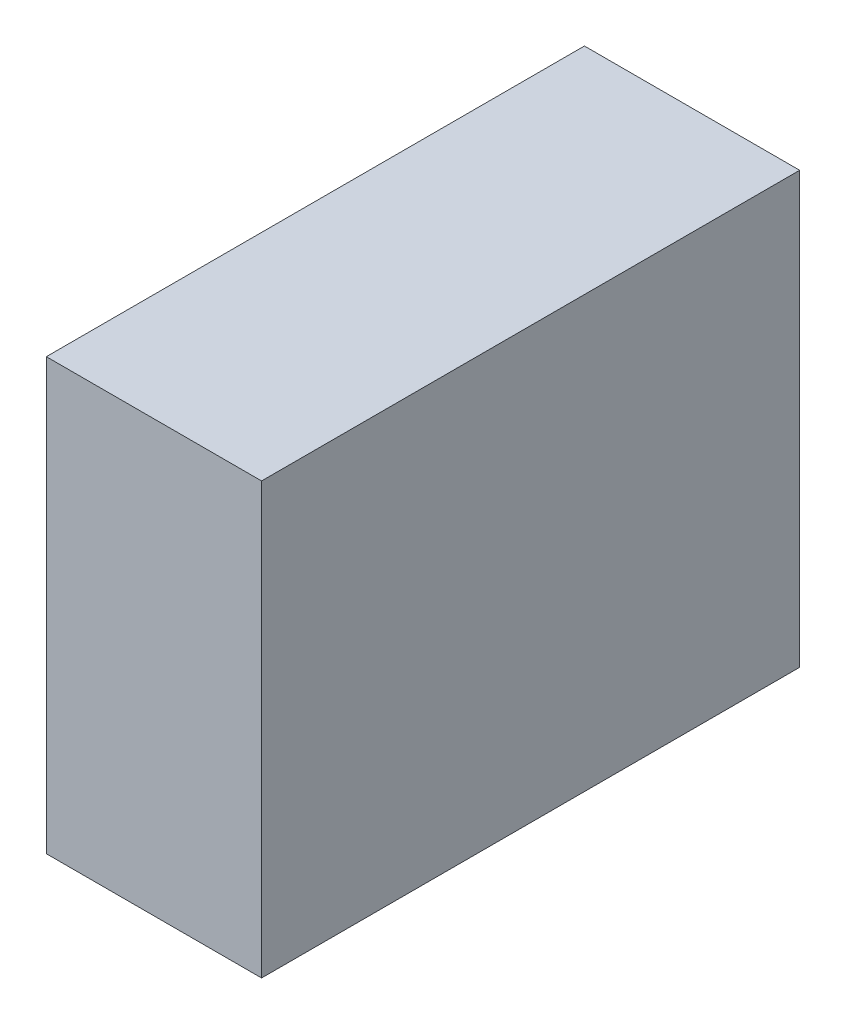
SolidWorks part; units mm, degrees
material "Pine"
ref_plane "Front Plane" through (0, 0, 0) normal (0, 0, 1) x (1, 0, 0)
ref_plane "Top Plane" through (0, 0, 0) normal (0, 1, 0) x (1, 0, 0)
ref_plane "Right Plane" through (0, 0, 0) normal (1, 0, 0) x (0, 0, -1)
sketch "Sketch1" plane through (0, 0, 0) normal (0, 0, 1) x (1, 0, 0)
  line L1 (0, 0) -> (38.1, 0)
  line L2 (0, 0) -> (0, 76.2)
  line L3 (0, 76.2) -> (38.1, 76.2)
  line L4 (38.1, 0) -> (38.1, 76.2)
  dimension "D1" = 76.2
  dimension "D2" = 38.1
extrude "Boss-Extrude1" add sketch "Sketch1" along normal blind 95.25
